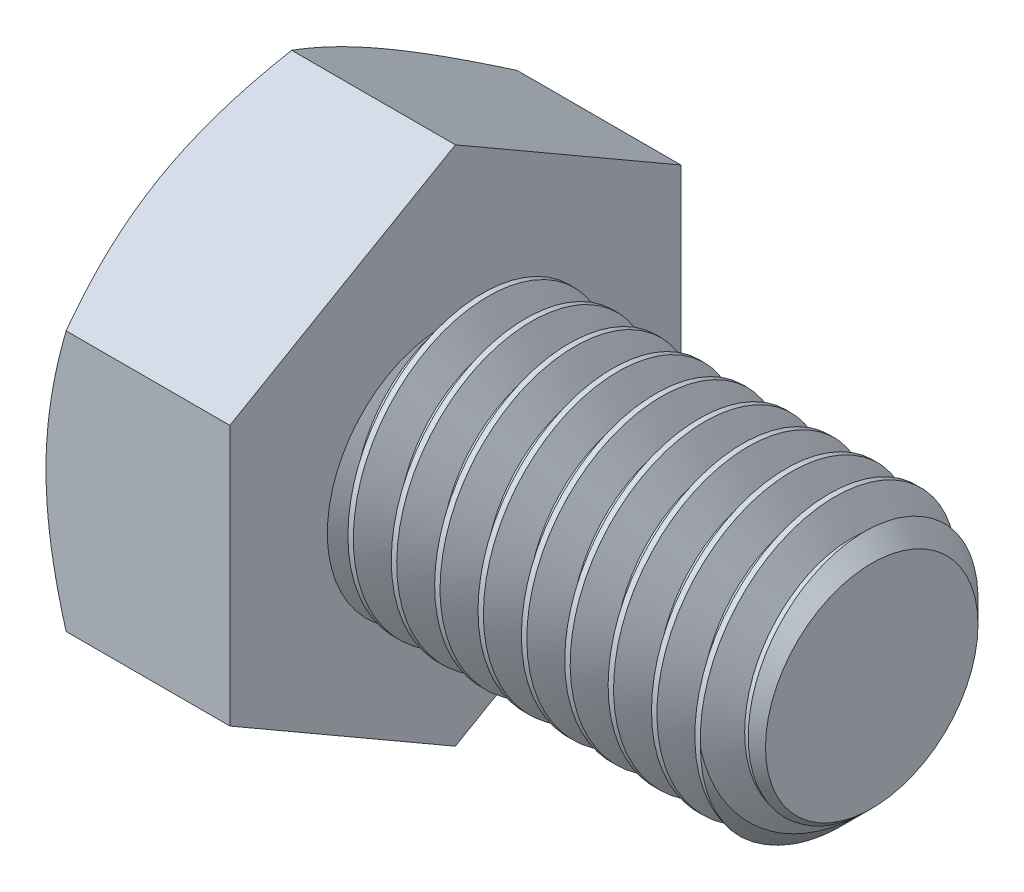
SolidWorks part; units mm, degrees
material "Stainless Steel (ferritic)"
ref_plane "Front Plane" through (0, 0, 0) normal (0, 0, 1) x (1, 0, 0)
ref_plane "Top Plane" through (0, 0, 0) normal (0, 1, 0) x (1, 0, 0)
ref_plane "Right Plane" through (0, 0, 0) normal (1, 0, 0) x (0, 0, -1)
sketch "Sketch1" plane through (0, 0, 0) normal (0, 0, 1) x (1, 0, 0)
  line L0 (-8.65, 0) -> (8.65, 0) construction
  line L1 (-3.35, 6.5) -> (-3.35, -6.5) construction
  line L2 (-8.65, 6.5) -> (-8.65, -6.5) construction
  line L3 (8.65, 4) -> (8.65, -4) construction
  point P8 (4.275, -4)
  dimension "Thread Dia" = 8
  dimension "Hex" = 13
  dimension "Head Ht" = 5.3
  dimension "Length" = 12
  dimension "D1" = 4.375
ref_plane "Plane2" through (8.65, 0, 0) normal (1, 0, 0) x (0, 0, -1)
sketch "Sketch2" plane through (8.65, 0, 0) normal (1, 0, 0) x (0, 0, -1)
  circle A0 centre (0, 0) radius 4
extrude "Boss-Extrude1" add sketch "Sketch2" against normal up to vertex (12 mm away) up to point (-3.35, -6.5, 0)
sketch "Sketch4" plane through (8.65, 0, 0) normal (1, 0, 0) x (0, 0, -1)
  circle A1 centre (0, 0) radius 4
  circle A2 centre (0, 0) radius 4
  dimension "D1" = 0
curve "Helix/Spiral1" pitch 1.25 height 13.25 turns 10.6 parameters "Pitch"=1.25
chamfer "Chamfer1" distance 0.9375 angle 45 1 edges at (8.65, 0, -4)
sketch "Sketch5" plane through (0, 0, 0) normal (0, 0, 1) x (1, 0, 0)
  line L0 (8.65, 4) -> (9.1187, 3.1881)
  line L1 (9.1187, 3.1881) -> (9.275, 3.1881)
  line L2 (9.275, 3.1881) -> (9.7437, 4)
  line L3 (8.65, 4) -> (9.7437, 4)
  line L4 (9.1969, 3.1881) -> (9.1969, 4) construction
  line L5 (8.8844, 3.5941) -> (9.5094, 3.5941) construction
  line L6 (8.65, -4) -> (8.65, 4) construction
  dimension "D1" = 60
  dimension "D2" = 0.1562
  dimension "D3" = 0.625
sweep "Cut-Sweep1" cut profiles "Sketch5" path "Helix/Spiral1" align with end faces yes
sketch "Sketch3" plane through (-3.35, 0, 0) normal (-1, 0, 0) x (0, 0, 1)
  line L0 (0, 6.5) -> (0, -6.5) construction
  line L1 (-6.5, -3.7528) -> (0, -7.5056)
  line L2 (0, -7.5056) -> (6.5, -3.7528)
  line L3 (6.5, -3.7528) -> (6.5, 3.7528)
  line L4 (6.5, 3.7528) -> (0, 7.5056)
  line L5 (0, 7.5056) -> (-6.5, 3.7528)
  line L6 (-6.5, 3.7528) -> (-6.5, -3.7528)
  circle A0 centre (0, 0) radius 6.5 construction
extrude "Boss-Extrude2" add sketch "Sketch3" along normal up to vertex (5.3 mm away) up to point (-8.65, -6.5, 0)
sketch "Sketch6" plane through (-8.65, 0, 0) normal (-1, 0, 0) x (0, 0, 1)
  circle A0 centre (0, 0) radius 6.5 construction
  circle A1 centre (0, 0) radius 6.5
extrude "Cut-Extrude1" cut sketch "Sketch6" against normal through all draft 60 flip side to cut
sketch "Sketch9" plane through (0, 0, 0) normal (0, 0, 1) x (1, 0, 0)
  line L0 (-3.35, 4) -> (-3.35, 0)
  line L1 (-3.35, 0) -> (-41.35, 0)
  line L2 (-41.35, 0) -> (-45.35, 4)
  line L3 (-45.35, 4) -> (-3.35, 4)
  line L4 (-8.65, 0) -> (8.65, 0) construction
  line L5 (-3.35, 6.5) -> (-3.35, -6.5) construction
  line L6 (8.65, 4) -> (8.65, -4) construction
  dimension "D1" = 45
  dimension "MinThreadLg" = 54
revolve "Revolve1" [suppressed] add sketch "Sketch9" angle 360 about L1
sketch "Sketch10" plane through (-3.35, 0, 0) normal (1, 0, 0) x (0, 0, -1)
  circle A0 centre (0, 0) radius 7.5056
  circle A1 centre (0, 0) radius 11.1125
  dimension "D1" = 22.225
equation "\"D2@Sketch5\" = \"Pitch@Helix/Spiral1\"*.125"
equation "\"D3@Sketch5\" = \"Pitch@Helix/Spiral1\"*.50"
equation "\"D3@Helix/Spiral1\" = \"Length@Sketch1\"+\"Pitch@Helix/Spiral1\""
equation "\"D1@Chamfer1\" = \"Pitch@Helix/Spiral1\"*.750"
equation "\"D1@Sketch1\" = \"Pitch@Helix/Spiral1\"*3.50"
